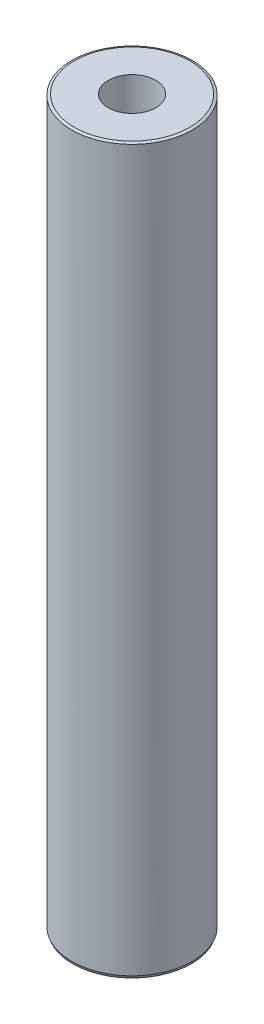
SolidWorks part; units mm, degrees
ref_plane "Front Plane" through (0, 0, 0) normal (0, 0, 1) x (1, 0, 0)
ref_plane "Top Plane" through (0, 0, 0) normal (0, 1, 0) x (1, 0, 0)
ref_plane "Right Plane" through (0, 0, 0) normal (1, 0, 0) x (0, 0, -1)
sketch "Sketch1" plane through (0, 0, 0) normal (0, 1, 0) x (1, 0, 0)
  circle A0 centre (0, 0) radius 50
  dimension "SHAFT_OD" = 100
extrude "Boss-Extrude1" add sketch "Sketch1" along normal blind 600
sketch "Sketch2" plane through (0, 0, 0) normal (0, 1, 0) x (1, 0, 0)
  circle A0 centre (0, 0) radius 19.7316
  dimension "BORE_D" = 39.4632
extrude "Cut-Extrude1" cut sketch "Sketch2" along normal through all
chamfer "Chamfer1" distance 0.8225 angle 69.065 2 edges at (0, 600, 50) (0, 0, 50) first distance on face at (0, 600, 50) first distance on face at (0, 0, 19.7316)
